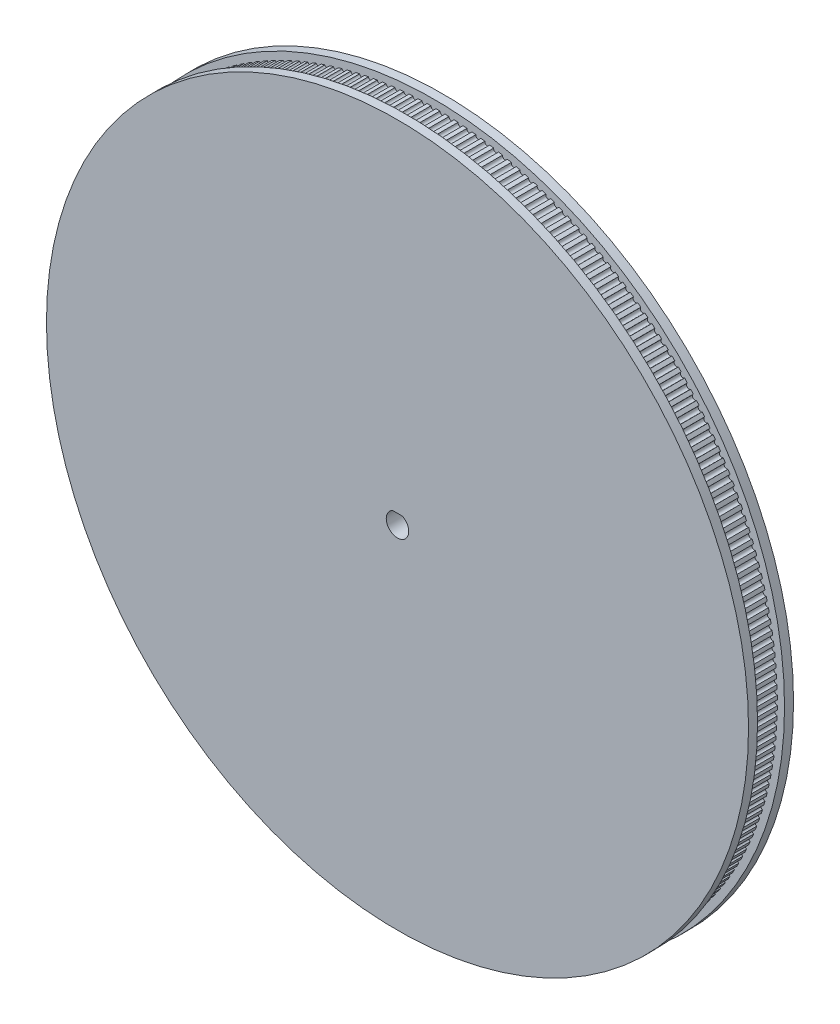
SolidWorks part; units mm, degrees
ref_plane "Vorne" through (0, 0, 0) normal (0, 0, 1) x (1, 0, 0)
ref_plane "Oben" through (0, 0, 0) normal (0, 1, 0) x (1, 0, 0)
ref_plane "Rechts" through (0, 0, 0) normal (1, 0, 0) x (0, 0, -1)
ref_plane "E_Boden" through (0, 1, 0) normal (0, 1, 0) x (1, 0, 0)
sketch "Skizze2" plane through (0, 0, 0) normal (0, 0, 1) x (1, 0, 0)
  circle A0 centre (0, 0) radius 76.395
  dimension "D1" = 152.79
extrude "Aufsatz-Linear austragen1" add sketch "Skizze2" along normal blind 6
sketch "Skizze3" plane through (0, 0, 6) normal (0, 0, 1) x (1, 0, 0)
  circle A0 centre (0, 76.395) radius 0.56
  circle A1 centre (0, 0) radius 76.395 construction
  circle A2 centre (1.9998, 76.3688) radius 0.56
  circle A3 centre (3.9982, 76.2903) radius 0.56
  circle A4 centre (5.9939, 76.1595) radius 0.56
  circle A5 centre (7.9855, 75.9765) radius 0.56
  circle A6 centre (9.9715, 75.7414) radius 0.56
  circle A7 centre (11.9508, 75.4545) radius 0.56
  circle A8 centre (13.9219, 75.1158) radius 0.56
  circle A9 centre (15.8834, 74.7256) radius 0.56
  circle A10 centre (17.8341, 74.2842) radius 0.56
  circle A11 centre (19.7725, 73.7919) radius 0.56
  circle A12 centre (21.6974, 73.249) radius 0.56
  circle A13 centre (23.6074, 72.656) radius 0.56
  circle A14 centre (25.5012, 72.0131) radius 0.56
  circle A15 centre (27.3775, 71.3209) radius 0.56
  circle A16 centre (29.2351, 70.5798) radius 0.56
  circle A17 centre (31.0726, 69.7903) radius 0.56
  circle A18 centre (32.8889, 68.953) radius 0.56
  circle A19 centre (34.6826, 68.0684) radius 0.56
  circle A20 centre (36.4525, 67.1372) radius 0.56
  circle A21 centre (38.1975, 66.16) radius 0.56
  circle A22 centre (39.9163, 65.1374) radius 0.56
  circle A23 centre (41.6077, 64.0702) radius 0.56
  circle A24 centre (43.2706, 62.9591) radius 0.56
  circle A25 centre (44.9039, 61.8049) radius 0.56
  circle A26 centre (46.5063, 60.6082) radius 0.56
  circle A27 centre (48.0769, 59.3701) radius 0.56
  circle A28 centre (49.6146, 58.0912) radius 0.56
  circle A29 centre (51.1182, 56.7725) radius 0.56
  circle A30 centre (52.5868, 55.415) radius 0.56
  circle A31 centre (54.0194, 54.0194) radius 0.56
  circle A32 centre (55.415, 52.5868) radius 0.56
  circle A33 centre (56.7725, 51.1182) radius 0.56
  circle A34 centre (58.0912, 49.6146) radius 0.56
  circle A35 centre (59.3701, 48.0769) radius 0.56
  circle A36 centre (60.6082, 46.5063) radius 0.56
  circle A37 centre (61.8049, 44.9039) radius 0.56
  circle A38 centre (62.9591, 43.2706) radius 0.56
  circle A39 centre (64.0702, 41.6077) radius 0.56
  circle A40 centre (65.1374, 39.9163) radius 0.56
  circle A41 centre (66.16, 38.1975) radius 0.56
  circle A42 centre (67.1372, 36.4525) radius 0.56
  circle A43 centre (68.0684, 34.6826) radius 0.56
  circle A44 centre (68.953, 32.8889) radius 0.56
  circle A45 centre (69.7903, 31.0726) radius 0.56
  circle A46 centre (70.5798, 29.2351) radius 0.56
  circle A47 centre (71.3209, 27.3775) radius 0.56
  circle A48 centre (72.0131, 25.5012) radius 0.56
  circle A49 centre (72.656, 23.6074) radius 0.56
  circle A50 centre (73.249, 21.6974) radius 0.56
  circle A51 centre (73.7919, 19.7725) radius 0.56
  circle A52 centre (74.2842, 17.8341) radius 0.56
  circle A53 centre (74.7256, 15.8834) radius 0.56
  circle A54 centre (75.1158, 13.9219) radius 0.56
  circle A55 centre (75.4545, 11.9508) radius 0.56
  circle A56 centre (75.7414, 9.9715) radius 0.56
  circle A57 centre (75.9765, 7.9855) radius 0.56
  circle A58 centre (76.1595, 5.9939) radius 0.56
  circle A59 centre (76.2903, 3.9982) radius 0.56
  circle A60 centre (76.3688, 1.9998) radius 0.56
  circle A61 centre (76.395, 0) radius 0.56
  circle A62 centre (76.3688, -1.9998) radius 0.56
  circle A63 centre (76.2903, -3.9982) radius 0.56
  circle A64 centre (76.1595, -5.9939) radius 0.56
  circle A65 centre (75.9765, -7.9855) radius 0.56
  circle A66 centre (75.7414, -9.9715) radius 0.56
  circle A67 centre (75.4545, -11.9508) radius 0.56
  circle A68 centre (75.1158, -13.9219) radius 0.56
  circle A69 centre (74.7256, -15.8834) radius 0.56
  circle A70 centre (74.2842, -17.8341) radius 0.56
  circle A71 centre (73.7919, -19.7725) radius 0.56
  circle A72 centre (73.249, -21.6974) radius 0.56
  circle A73 centre (72.656, -23.6074) radius 0.56
  circle A74 centre (72.0131, -25.5012) radius 0.56
  circle A75 centre (71.3209, -27.3775) radius 0.56
  circle A76 centre (70.5798, -29.2351) radius 0.56
  circle A77 centre (69.7903, -31.0726) radius 0.56
  circle A78 centre (68.953, -32.8889) radius 0.56
  circle A79 centre (68.0684, -34.6826) radius 0.56
  circle A80 centre (67.1372, -36.4525) radius 0.56
  circle A81 centre (66.16, -38.1975) radius 0.56
  circle A82 centre (65.1374, -39.9163) radius 0.56
  circle A83 centre (64.0702, -41.6077) radius 0.56
  circle A84 centre (62.9591, -43.2706) radius 0.56
  circle A85 centre (61.8049, -44.9039) radius 0.56
  circle A86 centre (60.6082, -46.5063) radius 0.56
  circle A87 centre (59.3701, -48.0769) radius 0.56
  circle A88 centre (58.0912, -49.6146) radius 0.56
  circle A89 centre (56.7725, -51.1182) radius 0.56
  circle A90 centre (55.415, -52.5868) radius 0.56
  circle A91 centre (54.0194, -54.0194) radius 0.56
  circle A92 centre (52.5868, -55.415) radius 0.56
  circle A93 centre (51.1182, -56.7725) radius 0.56
  circle A94 centre (49.6146, -58.0912) radius 0.56
  circle A95 centre (48.0769, -59.3701) radius 0.56
  circle A96 centre (46.5063, -60.6082) radius 0.56
  circle A97 centre (44.9039, -61.8049) radius 0.56
  circle A98 centre (43.2706, -62.9591) radius 0.56
  circle A99 centre (41.6077, -64.0702) radius 0.56
  circle A100 centre (39.9163, -65.1374) radius 0.56
  circle A101 centre (38.1975, -66.16) radius 0.56
  circle A102 centre (36.4525, -67.1372) radius 0.56
  circle A103 centre (34.6826, -68.0684) radius 0.56
  circle A104 centre (32.8889, -68.953) radius 0.56
  circle A105 centre (31.0726, -69.7903) radius 0.56
  circle A106 centre (29.2351, -70.5798) radius 0.56
  circle A107 centre (27.3775, -71.3209) radius 0.56
  circle A108 centre (25.5012, -72.0131) radius 0.56
  circle A109 centre (23.6074, -72.656) radius 0.56
  circle A110 centre (21.6974, -73.249) radius 0.56
  circle A111 centre (19.7725, -73.7919) radius 0.56
  circle A112 centre (17.8341, -74.2842) radius 0.56
  circle A113 centre (15.8834, -74.7256) radius 0.56
  circle A114 centre (13.9219, -75.1158) radius 0.56
  circle A115 centre (11.9508, -75.4545) radius 0.56
  circle A116 centre (9.9715, -75.7414) radius 0.56
  circle A117 centre (7.9855, -75.9765) radius 0.56
  circle A118 centre (5.9939, -76.1595) radius 0.56
  circle A119 centre (3.9982, -76.2903) radius 0.56
  circle A120 centre (1.9998, -76.3688) radius 0.56
  circle A121 centre (0, -76.395) radius 0.56
  circle A122 centre (-1.9998, -76.3688) radius 0.56
  circle A123 centre (-3.9982, -76.2903) radius 0.56
  circle A124 centre (-5.9939, -76.1595) radius 0.56
  circle A125 centre (-7.9855, -75.9765) radius 0.56
  circle A126 centre (-9.9715, -75.7414) radius 0.56
  circle A127 centre (-11.9508, -75.4545) radius 0.56
  circle A128 centre (-13.9219, -75.1158) radius 0.56
  circle A129 centre (-15.8834, -74.7256) radius 0.56
  circle A130 centre (-17.8341, -74.2842) radius 0.56
  circle A131 centre (-19.7725, -73.7919) radius 0.56
  circle A132 centre (-21.6974, -73.249) radius 0.56
  circle A133 centre (-23.6074, -72.656) radius 0.56
  circle A134 centre (-25.5012, -72.0131) radius 0.56
  circle A135 centre (-27.3775, -71.3209) radius 0.56
  circle A136 centre (-29.2351, -70.5798) radius 0.56
  circle A137 centre (-31.0726, -69.7903) radius 0.56
  circle A138 centre (-32.8889, -68.953) radius 0.56
  circle A139 centre (-34.6826, -68.0684) radius 0.56
  circle A140 centre (-36.4525, -67.1372) radius 0.56
  circle A141 centre (-38.1975, -66.16) radius 0.56
  circle A142 centre (-39.9163, -65.1374) radius 0.56
  circle A143 centre (-41.6077, -64.0702) radius 0.56
  circle A144 centre (-43.2706, -62.9591) radius 0.56
  circle A145 centre (-44.9039, -61.8049) radius 0.56
  circle A146 centre (-46.5063, -60.6082) radius 0.56
  circle A147 centre (-48.0769, -59.3701) radius 0.56
  circle A148 centre (-49.6146, -58.0912) radius 0.56
  circle A149 centre (-51.1182, -56.7725) radius 0.56
  circle A150 centre (-52.5868, -55.415) radius 0.56
  circle A151 centre (-54.0194, -54.0194) radius 0.56
  circle A152 centre (-55.415, -52.5868) radius 0.56
  circle A153 centre (-56.7725, -51.1182) radius 0.56
  circle A154 centre (-58.0912, -49.6146) radius 0.56
  circle A155 centre (-59.3701, -48.0769) radius 0.56
  circle A156 centre (-60.6082, -46.5063) radius 0.56
  circle A157 centre (-61.8049, -44.9039) radius 0.56
  circle A158 centre (-62.9591, -43.2706) radius 0.56
  circle A159 centre (-64.0702, -41.6077) radius 0.56
  circle A160 centre (-65.1374, -39.9163) radius 0.56
  circle A161 centre (-66.16, -38.1975) radius 0.56
  circle A162 centre (-67.1372, -36.4525) radius 0.56
  circle A163 centre (-68.0684, -34.6826) radius 0.56
  circle A164 centre (-68.953, -32.8889) radius 0.56
  circle A165 centre (-69.7903, -31.0726) radius 0.56
  circle A166 centre (-70.5798, -29.2351) radius 0.56
  circle A167 centre (-71.3209, -27.3775) radius 0.56
  circle A168 centre (-72.0131, -25.5012) radius 0.56
  circle A169 centre (-72.656, -23.6074) radius 0.56
  circle A170 centre (-73.249, -21.6974) radius 0.56
  circle A171 centre (-73.7919, -19.7725) radius 0.56
  circle A172 centre (-74.2842, -17.8341) radius 0.56
  circle A173 centre (-74.7256, -15.8834) radius 0.56
  circle A174 centre (-75.1158, -13.9219) radius 0.56
  circle A175 centre (-75.4545, -11.9508) radius 0.56
  circle A176 centre (-75.7414, -9.9715) radius 0.56
  circle A177 centre (-75.9765, -7.9855) radius 0.56
  circle A178 centre (-76.1595, -5.9939) radius 0.56
  circle A179 centre (-76.2903, -3.9982) radius 0.56
  circle A180 centre (-76.3688, -1.9998) radius 0.56
  circle A181 centre (-76.395, 0) radius 0.56
  circle A182 centre (-76.3688, 1.9998) radius 0.56
  circle A183 centre (-76.2903, 3.9982) radius 0.56
  circle A184 centre (-76.1595, 5.9939) radius 0.56
  circle A185 centre (-75.9765, 7.9855) radius 0.56
  circle A186 centre (-75.7414, 9.9715) radius 0.56
  circle A187 centre (-75.4545, 11.9508) radius 0.56
  circle A188 centre (-75.1158, 13.9219) radius 0.56
  circle A189 centre (-74.7256, 15.8834) radius 0.56
  circle A190 centre (-74.2842, 17.8341) radius 0.56
  circle A191 centre (-73.7919, 19.7725) radius 0.56
  circle A192 centre (-73.249, 21.6974) radius 0.56
  circle A193 centre (-72.656, 23.6074) radius 0.56
  circle A194 centre (-72.0131, 25.5012) radius 0.56
  circle A195 centre (-71.3209, 27.3775) radius 0.56
  circle A196 centre (-70.5798, 29.2351) radius 0.56
  circle A197 centre (-69.7903, 31.0726) radius 0.56
  circle A198 centre (-68.953, 32.8889) radius 0.56
  circle A199 centre (-68.0684, 34.6826) radius 0.56
  circle A200 centre (-67.1372, 36.4525) radius 0.56
  circle A201 centre (-66.16, 38.1975) radius 0.56
  circle A202 centre (-65.1374, 39.9163) radius 0.56
  circle A203 centre (-64.0702, 41.6077) radius 0.56
  circle A204 centre (-62.9591, 43.2706) radius 0.56
  circle A205 centre (-61.8049, 44.9039) radius 0.56
  circle A206 centre (-60.6082, 46.5063) radius 0.56
  circle A207 centre (-59.3701, 48.0769) radius 0.56
  circle A208 centre (-58.0912, 49.6146) radius 0.56
  circle A209 centre (-56.7725, 51.1182) radius 0.56
  circle A210 centre (-55.415, 52.5868) radius 0.56
  circle A211 centre (-54.0194, 54.0194) radius 0.56
  circle A212 centre (-52.5868, 55.415) radius 0.56
  circle A213 centre (-51.1182, 56.7725) radius 0.56
  circle A214 centre (-49.6146, 58.0912) radius 0.56
  circle A215 centre (-48.0769, 59.3701) radius 0.56
  circle A216 centre (-46.5063, 60.6082) radius 0.56
  circle A217 centre (-44.9039, 61.8049) radius 0.56
  circle A218 centre (-43.2706, 62.9591) radius 0.56
  circle A219 centre (-41.6077, 64.0702) radius 0.56
  circle A220 centre (-39.9163, 65.1374) radius 0.56
  circle A221 centre (-38.1975, 66.16) radius 0.56
  circle A222 centre (-36.4525, 67.1372) radius 0.56
  circle A223 centre (-34.6826, 68.0684) radius 0.56
  circle A224 centre (-32.8889, 68.953) radius 0.56
  circle A225 centre (-31.0726, 69.7903) radius 0.56
  circle A226 centre (-29.2351, 70.5798) radius 0.56
  circle A227 centre (-27.3775, 71.3209) radius 0.56
  circle A228 centre (-25.5012, 72.0131) radius 0.56
  circle A229 centre (-23.6074, 72.656) radius 0.56
  circle A230 centre (-21.6974, 73.249) radius 0.56
  circle A231 centre (-19.7725, 73.7919) radius 0.56
  circle A232 centre (-17.8341, 74.2842) radius 0.56
  circle A233 centre (-15.8834, 74.7256) radius 0.56
  circle A234 centre (-13.9219, 75.1158) radius 0.56
  circle A235 centre (-11.9508, 75.4545) radius 0.56
  circle A236 centre (-9.9715, 75.7414) radius 0.56
  circle A237 centre (-7.9855, 75.9765) radius 0.56
  circle A238 centre (-5.9939, 76.1595) radius 0.56
  circle A239 centre (-3.9982, 76.2903) radius 0.56
  circle A240 centre (-1.9998, 76.3688) radius 0.56
  point P484 (0, 0)
  dimension "D1" = 1.12
  dimension "D2" = 240
extrude "Schnitt-Linear austragen3" cut sketch "Skizze3" against normal through all
sketch "Skizze4" plane through (0, 0, 0) normal (0, 0, -1) x (-1, 0, 0)
  circle A0 centre (0, 0) radius 78
  dimension "D1" = 156
extrude "Aufsatz-Linear austragen2" add sketch "Skizze4" along normal blind 2
sketch "Skizze5" plane through (0, 0, 6) normal (0, 0, 1) x (1, 0, 0)
  circle A0 centre (0, 0) radius 78
  dimension "D1" = 156
extrude "Aufsatz-Linear austragen3" add sketch "Skizze5" along normal blind 2
sketch "Skizze6" plane through (0, 0, 8) normal (0, 0, 1) x (1, 0, 0)
  line L0 (0, 78) -> (0, -78) construction
  line L1 (-78, 0) -> (78, 0) construction
  line L2 (-20.7727, 2.25) -> (23.9017, 2.25) construction
  line L3 (-1.0897, 2.25) -> (1.0897, 2.25)
  circle A0 centre (0, 0) radius 78 construction
  arc A1 (-1.0897, 2.25) -> (1.0897, 2.25) centre (0, 0) ccw
  dimension "D2" = 2.5
  dimension "D1" = 2.25
extrude "Schnitt-Linear austragen4" cut sketch "Skizze6" against normal through all
